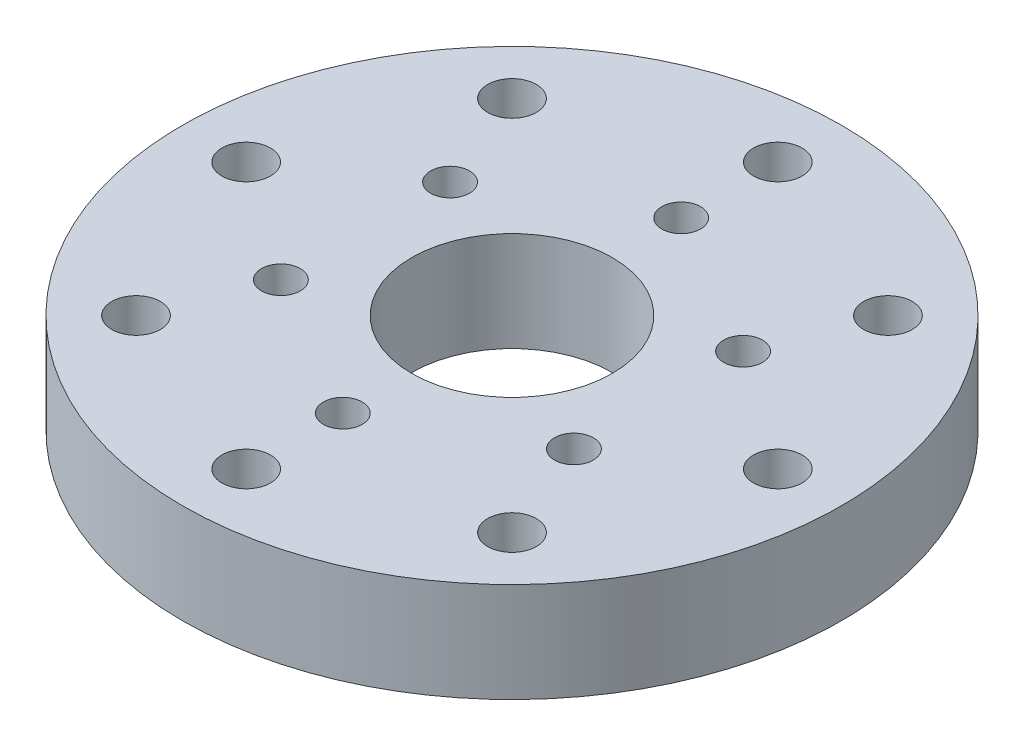
SolidWorks part; units mm, degrees
ref_plane "Front Plane" through (0, 0, 0) normal (0, 0, 1) x (1, 0, 0)
ref_plane "Top Plane" through (0, 0, 0) normal (0, 1, 0) x (1, 0, 0)
ref_plane "Right Plane" through (0, 0, 0) normal (1, 0, 0) x (0, 0, -1)
sketch "Sketch1" plane through (0, 0, 0) normal (0, 1, 0) x (1, 0, 0)
  circle A0 centre (0, 0) radius 57.15
  dimension "D1" = 114.3
extrude "Extrude1" add sketch "Sketch1" along normal blind 17.272
sketch "Sketch2" plane through (0, 0, 0) normal (0, 1, 0) x (1, 0, 0)
  circle A0 centre (0, 0) radius 17.399
  dimension "D1" = 34.798
extrude "Cut-Extrude1" cut sketch "Sketch2" along normal blind 22.352
sketch "Sketch3" plane through (0, 0, 0) normal (0, 1, 0) x (1, 0, 0)
  circle A0 centre (0, 29.337) radius 3.3655
  dimension "D1" = 29.337
  dimension "D2" = 6.731
extrude "Cut-Extrude3" cut sketch "Sketch3" along normal blind 22.352
ref_axis "Axis1" through (0, 103.9235, 0) along (0, -1, 0)
pattern_circular "CirPattern1" count 6 over 360 about axis through (0, 103.9235, 0) along (0, -1, 0) of "Cut-Extrude3"
sketch "Sketch4" plane through (0, 0, 0) normal (0, 1, 0) x (1, 0, 0)
  circle A0 centre (0, 46.101) radius 4.2164
  dimension "D1" = 46.101
extrude "Cut-Extrude4" cut sketch "Sketch4" along normal blind 22.352
pattern_circular "CirPattern2" count 8 over 360 about axis through (0, 103.9235, 0) along (0, -1, 0) of "Cut-Extrude4"
